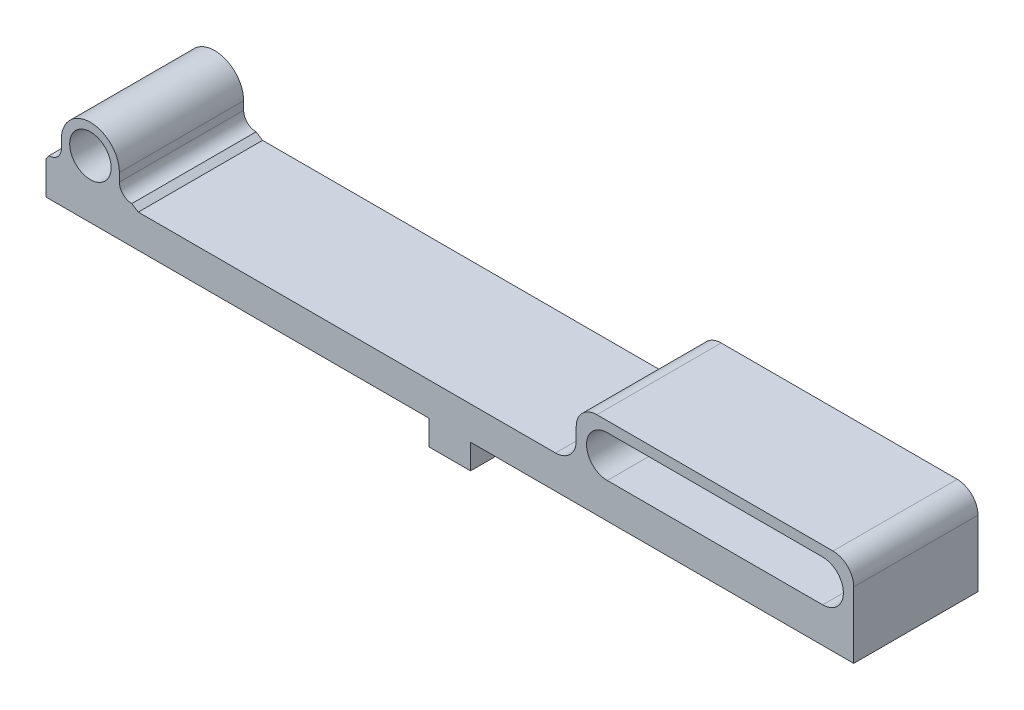
SolidWorks part; units mm, degrees
ref_plane "Front Plane" through (0, 0, 0) normal (0, 0, 1) x (1, 0, 0)
ref_plane "Top Plane" through (0, 0, 0) normal (0, 1, 0) x (1, 0, 0)
ref_plane "Right Plane" through (0, 0, 0) normal (1, 0, 0) x (0, 0, -1)
sketch "Sketch1" plane through (0, 0, 0) normal (0, 1, 0) x (1, 0, 0)
  line L1 (0, 0) -> (195, 0)
  line L2 (0, 0) -> (0, 30)
  line L3 (0, 30) -> (195, 30)
  line L4 (195, 0) -> (195, 30)
  dimension "D1" = 195
  dimension "D2" = 30
extrude "Boss-Extrude1" add sketch "Sketch1" along normal blind 8
sketch "Sketch2" plane through (0, 8, 0) normal (0, 1, 0) x (1, 0, 0)
  line L0 (195, 30) -> (0, 30) construction
  line L1 (4.7153, 30) -> (16.7153, 30)
  line L2 (4.7153, 30) -> (4.7153, 0)
  line L3 (4.7153, 0) -> (16.7153, 0)
  line L4 (16.7153, 30) -> (16.7153, 0)
  line L5 (0, 0) -> (195, 0) construction
  dimension "D1" = 12
extrude "Boss-Extrude2" add sketch "Sketch2" along normal blind 12
sketch "Sketch4" plane through (0, 0, -30) normal (0, 0, -1) x (-1, 0, 0)
  line L0 (-16.7153, 20) -> (-4.7153, 20) construction
  line L1 (-4.7153, 20) -> (-4.7153, 8) construction
  circle A0 centre (-10.7153, 14) radius 5
  dimension "D1" = 6
  dimension "D2" = 6
extrude "Cut-Extrude1" cut sketch "Sketch4" against normal through all
fillet "Fillet1" radius 4 2 edges at (4.7153, 8, -15) (16.7153, 8, -15)
fillet "Fillet2" radius 6 2 edges at (4.7153, 20, -15) (16.7153, 20, -15)
sketch "Sketch11" plane through (0, 0, -30) normal (0, 0, -1) x (-1, 0, 0)
  line L0 (-16.7153, 14) -> (-16.7153, 12) construction
  line L2 (-4.7153, 14) -> (-4.7153, 12) construction
  line L3 (-16.7153, 14) -> (-16.7153, 12)
  line L4 (-4.7153, 14) -> (-4.7153, 12)
  line L5 (-17.7153, 14) -> (-17.7153, 12)
  line L6 (-3.7153, 14) -> (-3.7153, 12)
  line L7 (-20.7153, 9) -> (-22.2788, 8)
  line L8 (-20.7153, 8) -> (-195, 8) construction
  line L9 (-22.2788, 8) -> (-20.7153, 8)
  line L10 (-0.7153, 9) -> (0, 8)
  line L11 (0, 8) -> (-0.7153, 8)
  arc A4 (-4.7153, 14) -> (-10.7153, 20) centre (-10.7153, 14) ccw construction
  arc A5 (-10.7153, 20) -> (-16.7153, 14) centre (-10.7153, 14) ccw construction
  arc A6 (-20.7153, 8) -> (-16.7153, 12) centre (-20.7153, 12) ccw construction
  arc A7 (-4.7153, 12) -> (-0.7153, 8) centre (-0.7153, 12) ccw construction
  arc A8 (-20.7153, 8) -> (-16.7153, 12) centre (-20.7153, 12) ccw
  arc A9 (-4.7153, 12) -> (-0.7153, 8) centre (-0.7153, 12) ccw
  arc A10 (-4.7153, 14) -> (-10.7153, 20) centre (-10.7153, 14) ccw
  arc A11 (-10.7153, 20) -> (-16.7153, 14) centre (-10.7153, 14) ccw
  arc A12 (-20.7153, 9) -> (-17.7153, 12) centre (-20.7153, 12) ccw
  arc A13 (-10.7153, 21) -> (-17.7153, 14) centre (-10.7153, 14) ccw
  arc A14 (-3.7153, 14) -> (-10.7153, 21) centre (-10.7153, 14) ccw
  arc A15 (-3.7153, 12) -> (-0.7153, 9) centre (-0.7153, 12) ccw
  dimension "D1" = 1
extrude "Boss-Extrude4" add sketch "Sketch11" against normal up to surface (30 mm away) up to face at (5.7153, 14, 0)
sketch "Sketch15" plane through (0, 8, 0) normal (0, 1, 0) x (1, 0, 0)
  line L0 (195, 15) -> (22.2788, 15) construction
  line L1 (195, 30) -> (128, 30)
  line L2 (195, 30) -> (195, 23)
  line L3 (195, 23) -> (128, 23)
  line L4 (128, 30) -> (128, 23)
  line L5 (195, 0) -> (195, 30) construction
  line L6 (22.2788, 0) -> (22.2788, 30) construction
  line L7 (195, 7) -> (128, 7)
  line L8 (128, 0) -> (128, 7)
  line L9 (195, 0) -> (128, 0)
  line L10 (195, 0) -> (195, 7)
  dimension "D1" = 7
  dimension "D2" = 67
extrude "Boss-Extrude6" add sketch "Sketch15" along normal blind 13
sketch "Sketch16" plane through (0, 0, -30) normal (0, 0, -1) x (-1, 0, 0)
  line L0 (-195, 21) -> (-195, 0) construction
  line L1 (-192.5, 18.5) -> (-130.5, 18.5)
  line L2 (-192.5, 18.5) -> (-192.5, 8.5)
  line L3 (-192.5, 8.5) -> (-130.5, 8.5)
  line L4 (-130.5, 18.5) -> (-130.5, 8.5)
  line L5 (-128, 21) -> (-128, 8) construction
  line L6 (-195, 21) -> (-128, 21) construction
  dimension "D1" = 2.5
  dimension "D2" = 2.5
  dimension "D3" = 10
  dimension "D4" = 2.5
extrude "Cut-Extrude4" cut sketch "Sketch16" against normal through all
fillet "Fillet5" radius 5 4 edges at (130.5, 18.5, -26.5) (130.5, 8.5, -26.5) (192.5, 18.5, -26.5) (192.5, 8.5, -26.5)
fillet "Fillet6" radius 5 2 edges at (195, 21, -26.5) (128, 21, -26.5)
fillet "Fillet7" radius 5 1 edges at (128, 8, -26.5)
sketch "Sketch17" plane through (0, 0, 0) normal (0, -1, 0) x (1, 0, 0)
  line L0 (0, 0) -> (195, 0) construction
  line L1 (92.5, 0) -> (102.5, 0)
  line L2 (92.5, 0) -> (92.5, -30)
  line L3 (92.5, -30) -> (102.5, -30)
  line L4 (102.5, 0) -> (102.5, -30)
  line L5 (195, -30) -> (0, -30) construction
  line L6 (0, -30) -> (0, 0) construction
  dimension "D1" = 10
  dimension "D2" = 92.5
extrude "Boss-Extrude7" add sketch "Sketch17" along normal blind 6
fillet "Fillet8" radius 5 6 edges at (195, 21, -3.5) (128, 21, -3.5) (192.5, 18.5, -3.5) (192.5, 8.5, -3.5) (130.5, 18.5, -3.5) (130.5, 8.5, -3.5)
fillet "Fillet9" radius 5 1 edges at (128, 8, -3.5)
sketch "Sketch20" plane through (0, 0, -23) normal (0, 0, 1) x (1, 0, 0)
  line L2 (135.5, 8.5) -> (187.5, 8.5)
  line L3 (187.5, 18.5) -> (135.5, 18.5)
  line L4 (135.5, 8.5) -> (187.5, 8.5)
  line L5 (187.5, 18.5) -> (135.5, 18.5)
  line L18 (195, 0) -> (195, 16)
  line L19 (190, 21) -> (133, 21)
  line L20 (128, 16) -> (128, 13)
  line L21 (123, 8) -> (22.2788, 8)
  line L22 (22.2788, 8) -> (20.7153, 9)
  line L23 (17.7153, 12) -> (17.7153, 14)
  line L24 (3.7153, 14) -> (3.7153, 12)
  line L25 (0.7153, 9) -> (0, 8)
  line L26 (0, 8) -> (0, 0)
  line L27 (0, 0) -> (92.5, 0)
  line L28 (92.5, 0) -> (92.5, -6)
  line L29 (92.5, -6) -> (102.5, -6)
  line L30 (102.5, -6) -> (102.5, 0)
  line L31 (102.5, 0) -> (195, 0)
  line L32 (195, 0) -> (195, 16)
  line L33 (190, 21) -> (133, 21)
  line L34 (128, 16) -> (128, 13)
  line L35 (123, 8) -> (22.2788, 8)
  line L36 (22.2788, 8) -> (20.7153, 9)
  line L37 (17.7153, 12) -> (17.7153, 14)
  line L38 (3.7153, 14) -> (3.7153, 12)
  line L39 (0.7153, 9) -> (0, 8)
  line L40 (0, 8) -> (0, 0)
  line L41 (0, 0) -> (92.5, 0)
  line L42 (92.5, 0) -> (92.5, -6)
  line L43 (92.5, -6) -> (102.5, -6)
  line L44 (102.5, -6) -> (102.5, 0)
  line L45 (102.5, 0) -> (195, 0)
  circle A1 centre (10.7153, 14) radius 5
  circle A2 centre (10.7153, 14) radius 5
  arc A6 (130.5, 13.5) -> (135.5, 8.5) centre (135.5, 13.5) ccw
  arc A7 (135.5, 18.5) -> (130.5, 13.5) centre (135.5, 13.5) ccw
  arc A8 (192.5, 13.5) -> (187.5, 18.5) centre (187.5, 13.5) ccw
  arc A9 (187.5, 8.5) -> (192.5, 13.5) centre (187.5, 13.5) ccw
  arc A10 (130.5, 13.5) -> (135.5, 8.5) centre (135.5, 13.5) ccw
  arc A11 (135.5, 18.5) -> (130.5, 13.5) centre (135.5, 13.5) ccw
  arc A12 (192.5, 13.5) -> (187.5, 18.5) centre (187.5, 13.5) ccw
  arc A13 (187.5, 8.5) -> (192.5, 13.5) centre (187.5, 13.5) ccw
  arc A16 (195, 16) -> (190, 21) centre (190, 16) ccw
  arc A17 (133, 21) -> (128, 16) centre (133, 16) ccw
  arc A18 (123, 8) -> (128, 13) centre (123, 13) ccw
  arc A19 (17.7153, 12) -> (20.7153, 9) centre (20.7153, 12) ccw
  arc A20 (17.7153, 14) -> (3.7153, 14) centre (10.7153, 14) ccw
  arc A21 (0.7153, 9) -> (3.7153, 12) centre (0.7153, 12) ccw
  arc A22 (195, 16) -> (190, 21) centre (190, 16) ccw
  arc A23 (133, 21) -> (128, 16) centre (133, 16) ccw
  arc A24 (123, 8) -> (128, 13) centre (123, 13) ccw
  arc A25 (17.7153, 12) -> (20.7153, 9) centre (20.7153, 12) ccw
  arc A26 (17.7153, 14) -> (3.7153, 14) centre (10.7153, 14) ccw
  arc A27 (0.7153, 9) -> (3.7153, 12) centre (0.7153, 12) ccw
  dimension "D1" = 0
  dimension "D2" = 0
  dimension "D3" = 0
extrude "Boss-Extrude8" add sketch "Sketch20" along normal up to surface (16 mm away) up to face at (161.5, 13.5, -7)
